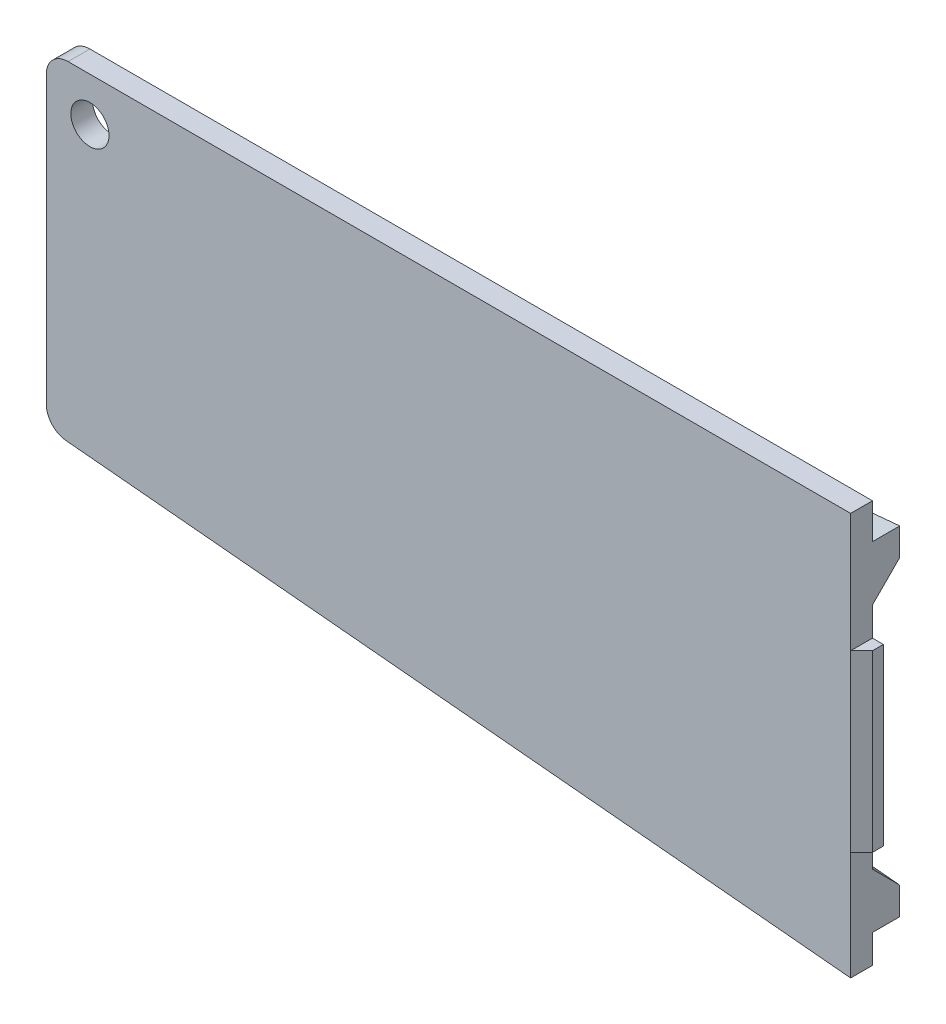
SolidWorks part; units mm, degrees
ref_plane "Front Plane" through (0, 0, 0) normal (0, 0, 1) x (1, 0, 0)
ref_plane "Top Plane" through (0, 0, 0) normal (0, 1, 0) x (1, 0, 0)
ref_plane "Right Plane" through (0, 0, 0) normal (1, 0, 0) x (0, 0, -1)
sketch "Sketch1" plane through (0, 0, 0) normal (0, 0, 1) x (1, 0, 0)
  line L0 (-116.7016, -4.6777) -> (-116.7016, -1) construction
  line L1 (-43, -35.8676) -> (-43, 1)
  line L4 (-43, 1) -> (-114.7016, 1)
  line L7 (-130.0236, -27.7586) -> (-44.8144, -35.6986) construction
  line L8 (-43, -27.8997) -> (-43, -41) construction
  line L9 (-116.7016, -4.6777) -> (-116.7016, -1)
  line L11 (-1, 1) -> (-35, 1) construction
  line L14 (-130.0236, -27.7586) -> (-116.7016, -29) construction
  line L15 (-116.7016, -4.6777) -> (-116.7016, -27.1777)
  line L16 (-114.8872, -29.1691) -> (-43, -35.8676)
  arc A0 (-114.7016, 1) -> (-116.7016, -1) centre (-114.7016, -1) ccw construction
  arc A4 (-114.7016, 1) -> (-116.7016, -1) centre (-114.7016, -1) ccw
  arc A8 (-116.7016, -27.1777) -> (-114.8872, -29.1691) centre (-114.7016, -27.1777) ccw
extrude "Boss-Extrude1" add sketch "Sketch1" along normal blind 2
ref_plane "Plane1" through (0, -17.8997, 0) normal (0, -1, 0) x (-1, 0, 0)
sketch "Sketch3" plane through (0, -17.8997, 0) normal (0, -1, 0) x (-1, 0, 0)
  line L0 (42, -1) -> (42, 0)
  line L1 (42, -1) -> (43, -2)
  line L2 (42, 0) -> (41, 0) construction
  line L3 (41, 0) -> (43, -2)
  line L4 (43, -2) -> (43, 0)
  line L5 (43, 0) -> (41, 0)
  line L6 (41, 0) -> (42, -1) construction
  line L7 (43, -2) -> (43, 0)
  line L8 (43, 0) -> (42, 0)
  dimension "D2" = 1
  dimension "D1" = 0
extrude "Boss-Extrude2" add sketch "Sketch3" along normal mid plane 16
sketch "Sketch4" plane through (0, 0, 0) normal (0, 0, -1) x (-1, 0, 0)
  line L0 (35.8307, -34.0249) -> (112.3865, -26.8913) construction
  line L1 (114.2009, -24.8999) -> (114.2009, -10.6001) construction
  line L2 (112.3865, -8.6087) -> (36.0976, -1.5) construction
  line L3 (35.8307, -34.0249) -> (43, -33.3568) construction
  line L4 (114.2009, -24.8999) -> (114.2009, -10.6001) construction
  line L5 (112.3865, -8.6087) -> (43, -2.1432) construction
  line L6 (43, -2.1432) -> (43, -33.3568) construction
  line L7 (43, -35.8676) -> (43, -25.8997) construction
  line L8 (43, -2.1432) -> (36.0976, -1.5) construction
  line L9 (43, -33.3568) -> (112.3865, -26.8913) construction
  line L10 (35.8214, -33.9253) -> (42.9907, -33.2572) construction
  line L11 (42.9907, -33.2572) -> (43, -33.2564) construction
  line L12 (114.1009, -24.8999) -> (114.1009, -10.6001)
  line L13 (112.3772, -8.7083) -> (43, -2.2436)
  line L14 (42.9907, -2.2428) -> (36.0883, -1.5996) construction
  line L15 (35.5895, -31.4361) -> (42.7588, -30.768) construction
  line L16 (42.7588, -30.768) -> (43, -30.7456) construction
  line L17 (111.6009, -24.3532) -> (111.6009, -11.1468)
  line L18 (111.6009, -11.1468) -> (43, -4.7544)
  line L19 (42.7588, -4.732) -> (35.8563, -4.0888) construction
  line L20 (43, -2.2436) -> (42.9907, -2.2428) construction
  line L21 (43, -4.7544) -> (42.7588, -4.732) construction
  line L22 (111.6009, -11.1468) -> (42.7588, -4.732) construction
  line L23 (43, -9.8997) -> (43, 1) construction
  line L24 (112.3772, -8.7083) -> (42.9907, -2.2428) construction
  line L25 (43, -2.2436) -> (43, -4.7544)
  line L26 (43, -33.2564) -> (112.3772, -26.7917)
  line L27 (42.9907, -33.2572) -> (112.3772, -26.7917) construction
  line L28 (43, -30.7456) -> (111.6009, -24.3532)
  line L29 (42.7588, -30.768) -> (111.6009, -24.3532) construction
  line L30 (43, -30.7456) -> (43, -33.2564)
  arc A0 (112.3865, -26.8913) -> (114.2009, -24.8999) centre (112.2009, -24.8999) ccw construction
  arc A1 (114.2009, -10.6001) -> (112.3865, -8.6087) centre (112.2009, -10.6001) ccw construction
  arc A2 (112.3865, -26.8913) -> (114.2009, -24.8999) centre (112.2009, -24.8999) ccw construction
  arc A3 (114.2009, -10.6001) -> (112.3865, -8.6087) centre (112.2009, -10.6001) ccw construction
  arc A4 (112.3772, -26.7917) -> (114.1009, -24.8999) centre (112.2009, -24.8999) ccw
  arc A5 (114.1009, -10.6001) -> (112.3772, -8.7083) centre (112.2009, -10.6001) ccw
  arc A6 (111.6009, -24.3532) -> (111.6009, -24.3532) centre (111.6009, -24.3532) ccw
  arc A7 (111.6009, -11.1468) -> (111.6009, -11.1468) centre (111.6009, -11.1468) ccw
  dimension "D1" = 0.1
  dimension "D2" = 2.6
extrude "Boss-Extrude3" add sketch "Sketch4" along normal blind 2.5
chamfer "Chamfer1" distance 2.5 angle 45 3 edges at (-111.6009, -17.75, 0)
sketch "Sketch5" plane through (0, 0, 0) normal (0, 0, -1) x (-1, 0, 0)
  circle A0 centre (112.7016, -3) radius 1.75
  dimension "D1" = 3.5
extrude "Cut-Extrude1" cut sketch "Sketch5" against normal through all
